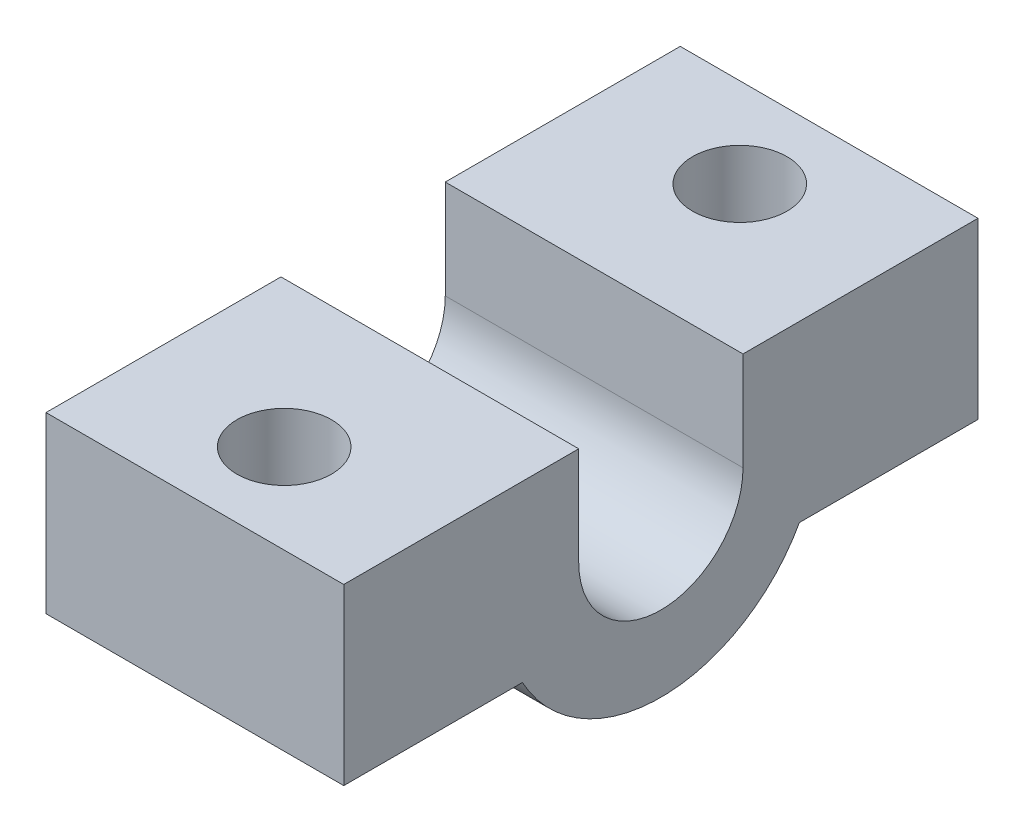
SolidWorks part; units mm, degrees
ref_plane "Front Plane" through (0, 0, 0) normal (0, 0, 1) x (1, 0, 0)
ref_plane "Top Plane" through (0, 0, 0) normal (0, 1, 0) x (1, 0, 0)
ref_plane "Right Plane" through (0, 0, 0) normal (1, 0, 0) x (0, 0, -1)
sketch "Sketch2" plane through (0, 0, 0) normal (1, 0, 0) x (0, 0, -1)
  line L0 (-10.035, 0) -> (10.035, 0) construction
  line L1 (-11.035, 0) -> (-42.6011, 0) construction
  line L2 (11.035, 0) -> (83.965, 0) construction
  line L3 (0, 0) -> (95, 0) construction
  line L4 (106.035, 0) -> (137.6011, 0) construction
  line L5 (-18.6011, -10.16) -> (-42.6011, -10.16)
  line L6 (18.6011, -10.16) -> (76.3989, -10.16) construction
  line L7 (113.6011, -10.16) -> (137.6011, -10.16) construction
  line L8 (-42.6011, 0) -> (-42.6011, -10.16)
  line L9 (137.6011, 0) -> (137.6011, -10.16) construction
  line L10 (-42.6011, 0) -> (-42.6011, 13.245)
  line L11 (-42.6011, 13.245) -> (-11.035, 13.245)
  line L12 (-11.035, 13.245) -> (-11.035, 0)
  line L13 (11.035, 0) -> (11.035, 13.245)
  line L14 (11.035, 13.245) -> (83.965, 13.245) construction
  line L15 (83.965, 13.245) -> (83.965, 0) construction
  line L16 (106.035, 0) -> (106.035, 13.245) construction
  line L17 (106.035, 13.245) -> (137.6011, 13.245) construction
  line L18 (137.6011, 13.245) -> (137.6011, 0) construction
  line L19 (11.035, 13.245) -> (42.6011, 13.245)
  line L20 (42.6011, 13.245) -> (42.6011, -10.16)
  line L21 (42.6011, -10.16) -> (18.6011, -10.16)
  arc A0 (-10.035, 0) -> (10.035, 0) centre (0, 0) ccw construction
  arc A1 (-11.035, 0) -> (11.035, 0) centre (0, 0) ccw
  arc A2 (84.965, 0) -> (105.035, 0) centre (95, 0) ccw construction
  arc A3 (83.965, 0) -> (106.035, 0) centre (95, 0) ccw construction
  arc A4 (-18.6011, -10.16) -> (18.6011, -10.16) centre (0, 0) ccw
  arc A5 (76.3989, -10.16) -> (113.6011, -10.16) centre (95, 0) ccw construction
  point P27 (35.1364, 13.24)
  dimension "D6" = 10.16
  dimension "D1" = 20.07
  dimension "D3" = 95
  dimension "D5" = 24
  dimension "D7" = 10.16
  dimension "D8" = 10.16
  dimension "D9" = 13.245
  dimension "D2" = 1
  dimension "D4" = 1
extrude "Boss-Extrude1" add sketch "Sketch2" along normal blind 40
sketch "Sketch3" plane through (0, 13.245, 0) normal (0, 1, 0) x (1, 0, 0)
  line L0 (0, -42.6011) -> (0, -18.6011) construction
  line L1 (0, -42.6011) -> (0, -18.6011) construction
  line L3 (40, -42.6011) -> (0, -42.6011) construction
  line L8 (40, -42.6011) -> (0, -42.6011) construction
  line L9 (40, -11.035) -> (40, -42.6011) construction
  circle A0 centre (20, -30.6011) radius 6.35
  circle A2 centre (20, 30.5989) radius 6.35
  point P6 (0, -30.6011)
  point P14 (20, -42.6011)
  point P15 (40, 78.76)
  point P16 (0, 0)
  point P17 (0, 0)
  point P23 (0, 0)
  dimension "D1" = 12.7
  dimension "D2" = 61.2
extrude "Cut-Extrude1" cut sketch "Sketch3" against normal up to next
